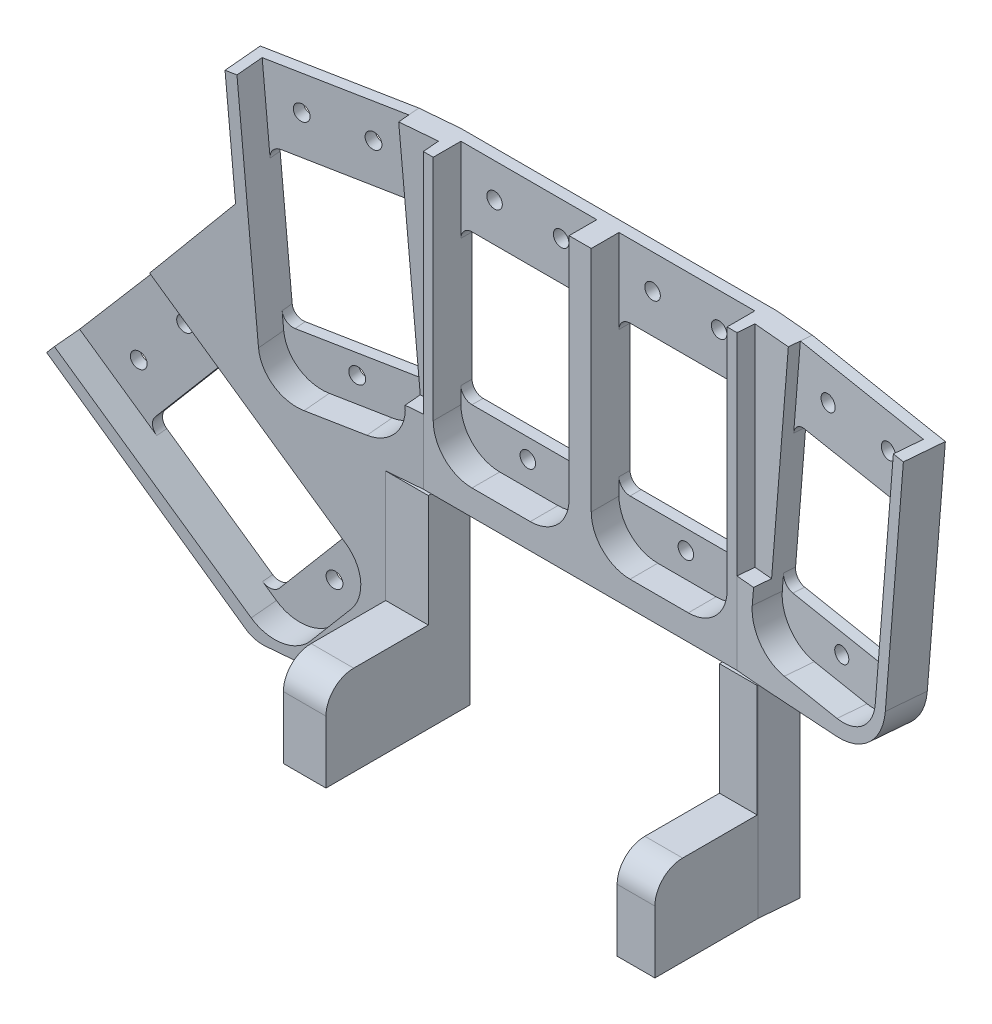
SolidWorks part; units mm, degrees
ref_plane "前视基准面" through (0, 0, 0) normal (0, 0, 1) x (1, 0, 0)
ref_plane "上视基准面" through (0, 0, 0) normal (0, 1, 0) x (1, 0, 0)
ref_plane "右视基准面" through (0, 0, 0) normal (1, 0, 0) x (0, 0, -1)
other "Configuration Table"
sketch "草图1" plane through (0, 0, 0) normal (0, 0, 1) x (1, 0, 0)
  line L0 (-6.3171, -14.436) -> (-6.3171, -11.436)
  line L1 (-8.3171, -13.436) -> (-28.8171, -13.436)
  line L2 (-30.8171, -11.436) -> (-30.8171, -14.436)
  line L3 (-23.8171, -21.436) -> (-13.3171, -21.436)
  line L4 (22.1829, -14.436) -> (22.1829, -11.436)
  line L5 (20.1829, -13.436) -> (-0.3171, -13.436)
  line L6 (-2.3171, -11.436) -> (-2.3171, -14.436)
  line L7 (4.6829, -21.436) -> (15.1829, -21.436)
  line L8 (22.1829, 11.564) -> (22.1829, 26.7199)
  line L9 (22.1829, 26.7199) -> (-2.3171, 26.7199)
  line L10 (-2.3171, 26.7199) -> (-2.3171, 11.564)
  line L11 (-0.3171, 13.564) -> (20.1829, 13.564)
  line L12 (-6.3171, 11.564) -> (-6.3171, 26.7199)
  line L13 (-6.3171, 26.7199) -> (-30.8171, 26.7199)
  line L14 (-30.8171, 26.7199) -> (-30.8171, 11.564)
  line L15 (-28.8171, 13.564) -> (-8.3171, 13.564)
  line L16 (-30.8171, 11.564) -> (-30.8171, -11.436)
  line L17 (-6.3171, 11.564) -> (-6.3171, -11.436)
  line L18 (22.1829, 11.564) -> (22.1829, -11.436)
  line L19 (-2.3171, 11.564) -> (-2.3171, -11.436)
  line L20 (-6.3171, 26.7199) -> (-2.3171, 26.7199)
  line L21 (-30.8171, 26.7199) -> (-32.8171, 26.7199)
  line L22 (-32.8171, 26.7199) -> (-32.8171, -25.4093)
  line L23 (-32.8171, -25.4093) -> (24.1829, -25.4093)
  line L24 (22.1829, 26.7199) -> (24.1829, 26.7199)
  line L25 (24.1829, 26.7199) -> (24.1829, -25.4093)
  arc A0 (-13.3171, -21.436) -> (-6.3171, -14.436) centre (-13.3171, -14.436) ccw
  arc A1 (-8.3171, -13.436) -> (-6.3171, -11.436) centre (-8.3171, -11.436) ccw
  arc A2 (-30.8171, -11.436) -> (-28.8171, -13.436) centre (-28.8171, -11.436) ccw
  arc A3 (-30.8171, -14.436) -> (-23.8171, -21.436) centre (-23.8171, -14.436) ccw
  arc A4 (15.1829, -21.436) -> (22.1829, -14.436) centre (15.1829, -14.436) ccw
  arc A5 (20.1829, -13.436) -> (22.1829, -11.436) centre (20.1829, -11.436) ccw
  arc A6 (-2.3171, -11.436) -> (-0.3171, -13.436) centre (-0.3171, -11.436) ccw
  arc A7 (-2.3171, -14.436) -> (4.6829, -21.436) centre (4.6829, -14.436) ccw
  arc A8 (-0.3171, 13.564) -> (-2.3171, 11.564) centre (-0.3171, 11.564) ccw
  arc A9 (22.1829, 11.564) -> (20.1829, 13.564) centre (20.1829, 11.564) ccw
  arc A10 (-28.8171, 13.564) -> (-30.8171, 11.564) centre (-28.8171, 11.564) ccw
  arc A11 (-6.3171, 11.564) -> (-8.3171, 13.564) centre (-8.3171, 11.564) ccw
sketch "草图2" plane through (0, 0, 0) normal (0, 0, 1) x (1, 0, 0)
  line L0 (-6.3171, -14.436) -> (-6.3171, -11.436)
  line L1 (-8.3171, -13.436) -> (-28.8171, -13.436)
  line L2 (-30.8171, -11.436) -> (-30.8171, -14.436)
  line L3 (-23.8171, -21.436) -> (-13.3171, -21.436)
  line L4 (22.1829, -14.436) -> (22.1829, -11.436)
  line L5 (20.1829, -13.436) -> (-0.3171, -13.436)
  line L6 (-2.3171, -11.436) -> (-2.3171, -14.436)
  line L7 (4.6829, -21.436) -> (15.1829, -21.436)
  line L8 (22.1829, 11.564) -> (22.1829, 26.7199)
  line L9 (22.1829, 26.7199) -> (-2.3171, 26.7199)
  line L10 (-2.3171, 26.7199) -> (-2.3171, 11.564)
  line L11 (-0.3171, 13.564) -> (20.1829, 13.564)
  line L12 (-6.3171, 11.564) -> (-6.3171, 26.7199)
  line L13 (-6.3171, 26.7199) -> (-30.8171, 26.7199)
  line L14 (-30.8171, 26.7199) -> (-30.8171, 11.564)
  line L15 (-28.8171, 13.564) -> (-8.3171, 13.564)
  line L16 (-30.8171, 11.564) -> (-30.8171, -11.436)
  line L17 (-6.3171, 11.564) -> (-6.3171, -11.436)
  line L18 (22.1829, 11.564) -> (22.1829, -11.436)
  line L19 (-2.3171, 11.564) -> (-2.3171, -11.436)
  line L20 (-6.3171, 26.7199) -> (-2.3171, 26.7199)
  line L21 (-30.8171, 26.7199) -> (-32.8171, 26.7199)
  line L22 (-32.8171, 26.7199) -> (-32.8171, -25.4093)
  line L23 (-32.8171, -25.4093) -> (24.1829, -25.4093)
  line L24 (22.1829, 26.7199) -> (24.1829, 26.7199)
  line L25 (24.1829, 26.7199) -> (24.1829, -25.4093)
  arc A0 (-13.3171, -21.436) -> (-6.3171, -14.436) centre (-13.3171, -14.436) ccw
  arc A1 (-8.3171, -13.436) -> (-6.3171, -11.436) centre (-8.3171, -11.436) ccw
  arc A2 (-30.8171, -11.436) -> (-28.8171, -13.436) centre (-28.8171, -11.436) ccw
  arc A3 (-30.8171, -14.436) -> (-23.8171, -21.436) centre (-23.8171, -14.436) ccw
  arc A4 (15.1829, -21.436) -> (22.1829, -14.436) centre (15.1829, -14.436) ccw
  arc A5 (20.1829, -13.436) -> (22.1829, -11.436) centre (20.1829, -11.436) ccw
  arc A6 (-2.3171, -11.436) -> (-0.3171, -13.436) centre (-0.3171, -11.436) ccw
  arc A7 (-2.3171, -14.436) -> (4.6829, -21.436) centre (4.6829, -14.436) ccw
  arc A8 (-0.3171, 13.564) -> (-2.3171, 11.564) centre (-0.3171, 11.564) ccw
  arc A9 (22.1829, 11.564) -> (20.1829, 13.564) centre (20.1829, 11.564) ccw
  arc A10 (-28.8171, 13.564) -> (-30.8171, 11.564) centre (-28.8171, 11.564) ccw
  arc A11 (-6.3171, 11.564) -> (-8.3171, 13.564) centre (-8.3171, 11.564) ccw
extrude "凸台-拉伸3" add sketch "草图1" along normal blind 2 contours A11 L12 L13 L14 A10 L15 | A9 L8 L9 L10 A8 L11 | L6 A7 L7 A4 L4 A5 L5 A6 | L2 A3 L3 A0 L0 A1 L1 A2 | A7 L6 L19 L10 L20 L12 L17 L0 A0 L3 A3 L2 L16 L14 L21 L22 L23 L25 L24 L8 L18 L4 A4 L7 region at (-18.5671, -17.1027, 0) region at (-4.3171, -7.8356, 0) region at (-18.5671, 20.1048, 0) region at (9.9329, 20.1048, 0) region at (9.9329, -17.1027, 0)
sketch "草图4" plane through (0, 0, 2) normal (0, 0, 1) x (1, 0, 0)
  line L0 (4.6829, -21.436) -> (15.1829, -21.436) construction
  line L1 (22.1829, -14.436) -> (22.1829, -11.436) construction
  line L2 (22.1829, 11.564) -> (22.1829, -11.436) construction
  line L3 (22.1829, 26.7199) -> (24.1829, 26.7199) construction
  line L4 (24.1829, 26.7199) -> (24.1829, -25.4093) construction
  line L5 (22.1829, 11.564) -> (22.1829, 26.7199) construction
  line L6 (-2.3171, 26.7199) -> (-2.3171, 11.564) construction
  line L7 (-2.3171, 11.564) -> (-2.3171, -11.436) construction
  line L8 (-2.3171, -11.436) -> (-2.3171, -14.436) construction
  line L9 (-32.8171, -25.4093) -> (24.1829, -25.4093) construction
  line L10 (-32.8171, 26.7199) -> (-32.8171, -25.4093) construction
  line L11 (-30.8171, 26.7199) -> (-32.8171, 26.7199) construction
  line L12 (-6.3171, 11.564) -> (-6.3171, 26.7199) construction
  line L13 (-6.3171, 11.564) -> (-6.3171, -11.436) construction
  line L14 (-6.3171, -14.436) -> (-6.3171, -11.436) construction
  line L15 (-23.8171, -21.436) -> (-13.3171, -21.436) construction
  line L16 (-30.8171, -11.436) -> (-30.8171, -14.436) construction
  line L17 (-30.8171, 11.564) -> (-30.8171, -11.436) construction
  line L18 (-30.8171, 26.7199) -> (-30.8171, 11.564) construction
  line L19 (4.6829, -21.436) -> (15.1829, -21.436)
  line L20 (22.1829, -14.436) -> (22.1829, -11.436)
  line L21 (22.1829, 11.564) -> (22.1829, -11.436)
  line L22 (22.1829, 26.7199) -> (24.1829, 26.7199)
  line L23 (24.1829, 26.7199) -> (24.1829, -25.4093)
  line L24 (22.1829, 11.564) -> (22.1829, 26.7199)
  line L25 (-2.3171, 26.7199) -> (-2.3171, 11.564)
  line L26 (-2.3171, 11.564) -> (-2.3171, -11.436)
  line L27 (-2.3171, -11.436) -> (-2.3171, -14.436)
  line L28 (-32.8171, -25.4093) -> (24.1829, -25.4093)
  line L29 (-32.8171, 26.7199) -> (-32.8171, -25.4093)
  line L30 (-30.8171, 26.7199) -> (-32.8171, 26.7199)
  line L31 (-6.3171, 11.564) -> (-6.3171, 26.7199)
  line L32 (-6.3171, 11.564) -> (-6.3171, -11.436)
  line L33 (-6.3171, -14.436) -> (-6.3171, -11.436)
  line L34 (-23.8171, -21.436) -> (-13.3171, -21.436)
  line L35 (-30.8171, -11.436) -> (-30.8171, -14.436)
  line L36 (-30.8171, 11.564) -> (-30.8171, -11.436)
  line L37 (-30.8171, 26.7199) -> (-30.8171, 11.564)
  line L38 (-6.3171, 26.7199) -> (-2.3171, 26.7199)
  arc A0 (15.1829, -21.436) -> (22.1829, -14.436) centre (15.1829, -14.436) ccw construction
  arc A1 (-2.3171, -14.436) -> (4.6829, -21.436) centre (4.6829, -14.436) ccw construction
  arc A2 (-13.3171, -21.436) -> (-6.3171, -14.436) centre (-13.3171, -14.436) ccw construction
  arc A3 (-30.8171, -14.436) -> (-23.8171, -21.436) centre (-23.8171, -14.436) ccw construction
  arc A4 (15.1829, -21.436) -> (22.1829, -14.436) centre (15.1829, -14.436) ccw
  arc A5 (-2.3171, -14.436) -> (4.6829, -21.436) centre (4.6829, -14.436) ccw
  arc A6 (-13.3171, -21.436) -> (-6.3171, -14.436) centre (-13.3171, -14.436) ccw
  arc A7 (-30.8171, -14.436) -> (-23.8171, -21.436) centre (-23.8171, -14.436) ccw
extrude "凸台-拉伸4" add sketch "草图4" along normal blind 5
sketch "草图5" plane through (0, 0, 2) normal (0, 0, 1) x (1, 0, 0)
  circle A0 centre (9.747, -16.936) radius 1.4
  circle A5 centre (-18.753, -16.936) radius 1.4
  circle A10 centre (-24.753, 20.564) radius 1.4
  circle A11 centre (-12.753, 20.564) radius 1.4
  circle A13 centre (3.747, 20.564) radius 1.4
  circle A14 centre (15.747, 20.564) radius 1.4
extrude "切除-拉伸1" cut sketch "草图5" against normal blind 5
sketch "草图7" plane through (0, 26.7199, 0) normal (0, 1, 0) x (1, 0, 0)
  line L0 (-32.8171, 0) -> (-70.2267, -3.2729)
  line L1 (-32.8171, -7) -> (-32.8171, 0) construction
  line L2 (-32.8171, 0) -> (-32.8171, -2)
  line L3 (-32.8171, -2) -> (-70.053, -5.2577)
  line L4 (-70.2267, -3.2729) -> (-70.053, -5.2577)
  dimension "D1" = 85
extrude "凸台-拉伸5" add sketch "草图7" against normal up to surface (52.1292 mm away) up to face at (-4.3171, -25.4093, 3.5)
sketch "草图8" plane through (-0.0756, 0, -0.8645) normal (0.0872, 0, 0.9962) x (0.9962, 0, -0.0872)
  line L0 (-36.1156, -14.2794) -> (-36.3771, -11.2908)
  line L2 (-60.7838, -13.4261) -> (-60.5224, -16.4147)
  line L4 (-38.3817, 11.6217) -> (-39.7026, 26.7199)
  line L5 (-39.7026, 26.7199) -> (-64.1093, 24.5846)
  line L6 (-64.1093, 24.5846) -> (-62.7884, 9.4864)
  line L8 (-62.7884, 9.4864) -> (-60.7838, -13.4261)
  line L9 (-38.3817, 11.6217) -> (-36.3771, -11.2908)
  line L10 (-70.2447, 26.7199) -> (-32.8666, 26.7199) construction
  line L11 (-36.1156, -14.2794) -> (-36.3771, -11.2908)
  line L12 (-38.1951, -13.4575) -> (-58.6171, -15.2442)
  line L13 (-52.9389, -22.7779) -> (-42.4789, -21.8628)
  line L14 (-60.9703, 11.6531) -> (-40.5484, 13.4398)
  line L15 (-38.3817, 11.6217) -> (-39.7026, 26.7199)
  arc A1 (-38.1951, -13.4575) -> (-36.3771, -11.2908) centre (-38.3695, -11.4651) ccw
  arc A2 (-60.7838, -13.4261) -> (-58.6171, -15.2442) centre (-58.7915, -13.2518) ccw
  arc A3 (-60.5224, -16.4147) -> (-52.9389, -22.7779) centre (-53.549, -15.8046) ccw
  arc A4 (-60.9703, 11.6531) -> (-62.7884, 9.4864) centre (-60.796, 9.6607) ccw
  arc A5 (-38.3817, 11.6217) -> (-40.5484, 13.4398) centre (-40.374, 11.4474) ccw
  circle A6 centre (-48.2863, -17.8537) radius 1.4
  arc A7 (-38.1951, -13.4575) -> (-36.3771, -11.2908) centre (-38.3695, -11.4651) ccw
  arc A8 (-42.4789, -21.8628) -> (-36.1156, -14.2794) centre (-43.089, -14.8894) ccw
  circle A9 centre (-57.5318, 18.9807) radius 1.4
  circle A10 centre (-45.5775, 20.0265) radius 1.4
  arc A11 (-38.3817, 11.6217) -> (-40.5484, 13.4398) centre (-40.374, 11.4474) ccw
extrude "切除-拉伸2" cut sketch "草图8" against normal blind 54 contours A9 | A10 | A6 | L9 A5 L14 A4 L8 A2 L12 A1 region at (-49.4697, -0.9022, 3.4569) region at (-48.1782, -17.8537, 3.3439) region at (-57.3885, 18.9807, 4.1497) region at (-45.4797, 20.0265, 3.1078)
sketch "草图9" plane through (-0.0756, 0, -0.8645) normal (0.0872, 0, 0.9962) x (0.9962, 0, -0.0872)
  line L0 (-38.3817, 11.6217) -> (-39.7026, 26.7199)
  line L1 (-70.2447, 26.7199) -> (-32.8666, 26.7199) construction
  line L2 (-39.7026, 26.7199) -> (-32.8666, 26.7199)
  line L3 (-32.8666, 26.7199) -> (-32.8666, -25.4093)
  line L4 (-32.8666, -25.4093) -> (-61.7354, -25.4093)
  line L5 (-60.7838, -13.4261) -> (-60.5224, -16.4147)
  line L6 (-60.7838, -13.4261) -> (-62.7884, 9.4864)
  line L7 (-62.7884, 9.4864) -> (-64.2962, 26.7199)
  line L8 (-64.2962, 26.7199) -> (-66.2962, 26.7199)
  line L9 (-66.2962, 26.7199) -> (-61.7354, -25.4093)
  line L10 (-60.7838, -13.4261) -> (-60.5224, -16.4147)
  line L11 (-36.1156, -14.2794) -> (-36.3771, -11.2908)
  line L13 (-52.9389, -22.7779) -> (-42.4789, -21.8628)
  line L14 (-38.3817, 11.6217) -> (-36.3771, -11.2908)
  circle A0 centre (-48.2863, -17.8537) radius 1.4
  arc A2 (-60.5224, -16.4147) -> (-52.9389, -22.7779) centre (-53.549, -15.8046) ccw
  arc A4 (-42.4789, -21.8628) -> (-36.1156, -14.2794) centre (-43.089, -14.8894) ccw
  line M17 (-70.2447, -25.4093) -> (-32.8666, -25.4093)
  line M18 (-32.8666, -25.4093) -> (-32.8666, 26.7199)
  line M19 (-32.8666, 26.7199) -> (-70.2447, 26.7199)
  line M22 (-38.3817, 11.6217) -> (-36.3771, -11.2908)
  line M26 (-60.7838, -13.4261) -> (-62.7884, 9.4864)
extrude "凸台-拉伸6" add sketch "草图9" along normal blind 5 contours A4 L13 A2 L5 L7 L9 L0 L11 M26 M19 M17 M18 M22 region at (-38.3546, 19.2248, 2.4845)
sketch "草图10" plane through (0, 26.7199, 0) normal (0, 1, 0) x (1, 0, 0)
  line L0 (24.1829, 0) -> (76.1307, -4.5448)
  line L1 (24.1829, -7) -> (24.1829, 0) construction
  line L3 (24.1829, -2) -> (76.1722, -6.5485)
  line L4 (76.1307, -4.5448) -> (76.1722, -6.5485)
  line L5 (24.1829, 0) -> (24.1829, -2)
  dimension "D1" = 85
extrude "凸台-拉伸7" add sketch "草图10" against normal up to surface (52.1292 mm away) up to face at (-35.0058, -25.4093, 4.568)
sketch "草图11" plane through (0.01, 0, -0.1148) normal (-0.0872, 0, 0.9962) x (0.9962, 0, 0.0872)
  line L0 (29.7802, 11.6217) -> (27.7757, -11.2908)
  line L1 (44.3375, -22.7779) -> (33.8775, -21.8628)
  line L2 (27.5142, -14.2794) -> (27.7757, -11.2908)
  line L3 (52.1824, -13.4261) -> (51.921, -16.4147)
  line L4 (57.6948, 26.7199) -> (53.134, -25.4093)
  line L5 (55.6948, 26.7199) -> (57.6948, 26.7199)
  line L6 (54.187, 9.4864) -> (55.6948, 26.7199)
  line L7 (52.1824, -13.4261) -> (54.187, 9.4864)
  line L8 (52.1824, -13.4261) -> (51.921, -16.4147)
  line L9 (24.2652, -25.4093) -> (53.134, -25.4093)
  line L10 (24.2652, 26.7199) -> (24.2652, -25.4093)
  line L11 (31.1012, 26.7199) -> (24.2652, 26.7199)
  line L12 (29.7802, 11.6217) -> (31.1012, 26.7199)
  arc A0 (33.8775, -21.8628) -> (27.5142, -14.2794) centre (34.4876, -14.8894) cw
  arc A1 (51.921, -16.4147) -> (44.3375, -22.7779) centre (44.9476, -15.8046) cw
  circle A2 centre (39.6849, -17.8537) radius 1.4
  line M1 (24.2652, -25.4093) -> (76.4531, -25.4093)
  line M3 (76.4531, 26.7199) -> (24.2652, 26.7199)
  line M4 (24.2652, 26.7199) -> (24.2652, -25.4093)
extrude "凸台-拉伸8" add sketch "草图11" along normal blind 5 contours L3 A1 L1 A0 L2 L0 L12 L4 L6 L7 M3 M4 M1 region at (28.0639, 0.2194, 2.3395)
sketch "草图12" plane through (0.01, 0, -0.1148) normal (-0.0872, 0, 0.9962) x (0.9962, 0, 0.0872)
  line L6 (50.0157, -15.2442) -> (29.5937, -13.4575)
  line L8 (31.9469, 13.4398) -> (52.3689, 11.6531)
  line L9 (29.7802, 11.6217) -> (27.7757, -11.2908)
  line L10 (54.187, 9.4864) -> (52.1824, -13.4261)
  circle A5 centre (36.6057, 20.0589) radius 1.4
  circle A6 centre (48.56, 19.0131) radius 1.4
  circle A7 centre (39.3145, -17.8213) radius 1.4
  arc A8 (27.7757, -11.2908) -> (29.5937, -13.4575) centre (29.768, -11.4651) ccw
  arc A10 (50.0157, -15.2442) -> (52.1824, -13.4261) centre (50.19, -13.2518) ccw
  arc A12 (54.187, 9.4864) -> (52.3689, 11.6531) centre (52.1946, 9.6607) ccw
  arc A13 (31.9469, 13.4398) -> (29.7802, 11.6217) centre (31.7726, 11.4474) ccw
extrude "切除-拉伸3" cut sketch "草图12" against normal blind 5
sketch "草图14" plane through (0, -25.4093, 0) normal (0, -1, 0) x (1, 0, 0)
  line L12 (52.5061, 9.4971) -> (23.9646, 7)
  line L13 (23.9646, 7) -> (-32.5988, 7)
  line L14 (-32.5988, 7) -> (-61.1404, 9.4971)
  line L15 (-61.1404, 9.4971) -> (-61.5762, 4.5161)
  line L16 (-61.5762, 4.5161) -> (-70.053, 5.2577)
  line L17 (-70.053, 5.2577) -> (-70.2267, 3.2729)
  line L18 (-70.2267, 3.2729) -> (-32.8171, 0)
  line L19 (-32.8171, 0) -> (24.1829, 0)
  line L20 (24.1829, 0) -> (76.1307, 4.5448)
  line L21 (76.1307, 4.5448) -> (76.1722, 6.5485)
  line L22 (76.1722, 6.5485) -> (52.9419, 4.5161)
  line L23 (52.9419, 4.5161) -> (52.5061, 9.4971)
  line L24 (52.5061, 9.4971) -> (23.9646, 7)
  line L26 (-32.5988, 7) -> (-61.1404, 9.4971)
  line L27 (-61.1404, 9.4971) -> (-61.5762, 4.5161)
  line L28 (-61.5762, 4.5161) -> (-70.053, 5.2577)
  line L29 (-70.053, 5.2577) -> (-70.2267, 3.2729)
  line L30 (-70.2267, 3.2729) -> (-32.8171, 0)
  line L31 (-32.8171, 0) -> (24.1829, 0)
  line L32 (24.1829, 0) -> (76.1307, 4.5448)
  line L33 (76.1307, 4.5448) -> (76.1722, 6.5485)
  line L34 (76.1722, 6.5485) -> (52.9419, 4.5161)
  line L35 (52.9419, 4.5161) -> (52.5061, 9.4971)
  line L36 (23.9646, 7) -> (-32.5988, 7)
  dimension "D1" = 0
extrude "凸台-拉伸9" add sketch "草图14" along normal blind 48
sketch "草图16" plane through (-69.9774, 0, 6.1222) normal (-0.9962, 0, 0.0872) x (0.0872, 0, 0.9962)
  line L4 (-2.8602, 26.7199) -> (-2.8602, -73.4093)
  line L5 (-2.8602, -73.4093) -> (-0.8678, -73.4093)
  line L6 (-0.8678, -73.4093) -> (-0.8678, 26.7199)
  line L7 (-0.8678, 26.7199) -> (-2.8602, 26.7199)
  line L8 (-2.8602, 26.7199) -> (-2.8602, -73.4093)
  line L9 (-2.8602, -73.4093) -> (-0.8678, -73.4093)
  line L10 (-0.8678, -73.4093) -> (-0.8678, 26.7199)
  line L11 (-0.8678, 26.7199) -> (-2.8602, 26.7199)
  dimension "D1" = 0
extrude "凸台-拉伸10" add sketch "草图16" along normal blind 31
sketch "草图19" plane through (-0.0756, 0, -0.8645) normal (0.0872, 0, 0.9962) x (0.9962, 0, -0.0872)
  line L5 (-66.2962, 26.7199) -> (-101.2447, 26.7199)
  line L6 (-101.2447, 26.7199) -> (-101.2447, -73.4093)
  line L7 (-101.2447, -73.4093) -> (-61.7354, -73.4093)
  line L8 (-61.7354, -73.4093) -> (-61.7354, -25.4093)
  line L9 (-61.7354, -25.4093) -> (-66.2962, 26.7199)
  line L10 (-66.2962, 26.7199) -> (-101.2447, 26.7199)
  line L11 (-101.2447, 26.7199) -> (-101.2447, -73.4093)
  line L12 (-101.2447, -73.4093) -> (-61.7354, -73.4093)
  line L13 (-61.7354, -73.4093) -> (-61.7354, -25.4093)
  line L14 (-61.7354, -25.4093) -> (-66.2962, 26.7199)
  dimension "D1" = 0
extrude "凸台-拉伸12" add sketch "草图19" along normal blind 5 contours L10 L11 L12 L13 L14
sketch "草图20" plane through (0.3601, 0, 4.1165) normal (0.0872, 0, 0.9962) x (0.9962, 0, -0.0872)
  line L0 (-45.9906, -40.369) -> (-48.2888, -38.4406)
  line L1 (-48.0423, -41.2583) -> (-61.2194, -56.9622)
  line L2 (-64.0371, -57.2087) -> (-61.7389, -59.1371)
  line L3 (-51.8771, -58.2743) -> (-45.1278, -50.2308)
  line L4 (-78.6472, -12.9668) -> (-94.4978, -31.6491)
  line L5 (-94.4978, -31.6491) -> (-81.6561, -42.4246)
  line L6 (-81.9026, -39.6069) -> (-68.7255, -23.903)
  line L7 (-65.9078, -23.6565) -> (-78.6472, -12.9668)
  line L8 (-81.6561, -42.4246) -> (-64.0371, -57.2087)
  line L9 (-65.9078, -23.6565) -> (-48.2888, -38.4406)
  arc A0 (-45.1278, -50.2308) -> (-45.9906, -40.369) centre (-50.4902, -45.7313) ccw
  arc A1 (-48.0423, -41.2583) -> (-48.2888, -38.4406) centre (-49.5744, -39.9727) ccw
  arc A2 (-64.0371, -57.2087) -> (-61.2194, -56.9622) centre (-62.7515, -55.6766) ccw
  arc A3 (-61.7389, -59.1371) -> (-51.8771, -58.2743) centre (-57.2394, -53.7747) ccw
  arc A4 (-81.9026, -39.6069) -> (-81.6561, -42.4246) centre (-80.3705, -40.8925) ccw
  arc A5 (-65.9078, -23.6565) -> (-68.7255, -23.903) centre (-67.1934, -25.1886) ccw
  circle A6 centre (-76.9391, -22.8016) radius 1.4
  circle A7 centre (-84.6526, -31.9941) radius 1.4
  circle A8 centre (-52.0692, -51.5024) radius 1.4
extrude "切除-拉伸4" cut sketch "草图20" against normal blind 5 contours L9 A5 L6 A4 L8 A2 L1 A1 | A6 | A7 | A5 L7 L4 L5 A4 L6 A7 A6 | L2 A3 L3 A0 L0 A1 L1 A2 A8 | A8 region at (-43.2922, -45.1476, 7.9356) region at (-64.3651, -40.4326, 9.7792) region at (-80.2633, -27.0578, 11.1701) region at (-76.2862, -22.8016, 10.8222) region at (-83.9703, -31.9941, 11.4944) region at (-51.5109, -51.5024, 8.6546)
sketch "草图22" plane through (-0.0756, 0, -0.8645) normal (0.0872, 0, 0.9962) x (0.9962, 0, -0.0872)
  circle A6 centre (-76.9391, -22.8016) radius 1.4
  circle A7 centre (-84.6526, -31.9941) radius 1.4
  circle A8 centre (-52.0692, -51.5024) radius 1.4
extrude "切除-拉伸5" cut sketch "草图22" against normal through all
sketch "草图23" plane through (-0.0756, 0, -0.8645) normal (0.0872, 0, 0.9962) x (0.9962, 0, -0.0872)
  line L1 (-48.0423, -41.2583) -> (-61.2194, -56.9622)
  line L6 (-81.9026, -39.6069) -> (-68.7255, -23.903)
  line L8 (-81.6561, -42.4246) -> (-64.0371, -57.2087)
  line L9 (-65.9078, -23.6565) -> (-48.2888, -38.4406)
  arc A1 (-48.0423, -41.2583) -> (-48.2888, -38.4406) centre (-49.5744, -39.9727) ccw
  arc A2 (-64.0371, -57.2087) -> (-61.2194, -56.9622) centre (-62.7515, -55.6766) ccw
  arc A4 (-81.9026, -39.6069) -> (-81.6561, -42.4246) centre (-80.3705, -40.8925) ccw
  arc A5 (-65.9078, -23.6565) -> (-68.7255, -23.903) centre (-67.1934, -25.1886) ccw
extrude "切除-拉伸6" cut sketch "草图23" against normal through all
sketch "草图24" plane through (0.3601, 0, 4.1165) normal (0.0872, 0, 0.9962) x (0.9962, 0, -0.0872)
  line L0 (-78.6472, -12.9668) -> (-94.4978, -31.6491)
  line L1 (-48.3684, -73.4093) -> (-101.2447, -73.4093)
  line L6 (-64.2962, 26.7199) -> (-101.2447, 26.7199) construction
  line L7 (-66.2962, 26.7199) -> (-64.3389, 4.3484)
  line L8 (-78.6472, -12.9668) -> (-64.3389, 4.3484)
  line L9 (-66.2962, 26.7199) -> (-101.2447, 26.7199)
  line L10 (-101.2447, 26.7199) -> (-101.2447, -73.4093)
  line L11 (-94.4978, -31.6491) -> (-95.7917, -33.1742)
  line L12 (-95.7917, -33.1742) -> (-48.3684, -73.4093)
  line L13 (-33.0849, -73.4093) -> (-101.2447, -73.4093) construction
extrude "切除-拉伸7" cut sketch "草图24" against normal through all
sketch "草图25" plane through (0, 0, 7) normal (0, 0, 1) x (1, 0, 0)
  line L8 (28.1628, -26.0179) -> (21.3541, -26.0179)
  line L9 (21.3541, -26.0179) -> (21.3541, -62.4789)
  line L10 (21.3541, -62.4789) -> (28.1628, -62.4789)
  line L11 (28.1628, -62.4789) -> (28.1628, -26.0179)
  line L12 (-38.8372, -62.4789) -> (-31.1575, -62.4789)
  line L13 (-31.1575, -62.4789) -> (-31.1575, -26.0179)
  line L14 (-31.1575, -26.0179) -> (-38.8372, -26.0179)
  line L15 (-38.8372, -26.0179) -> (-38.8372, -62.4789)
extrude "凸台-拉伸14" add sketch "草图25" along normal blind 19
sketch "草图26" plane through (0, 0, 7) normal (0, 0, 1) x (1, 0, 0)
  line L1 (-38.8372, -62.4789) -> (76.1722, -62.4789)
  line L2 (-38.8372, -62.4789) -> (-38.8372, -73.4093)
  line L3 (-38.8372, -73.4093) -> (76.1722, -73.4093)
  line L4 (76.1722, -62.4789) -> (76.1722, -73.4093)
  line L5 (-38.8372, -62.4789) -> (-63.6236, -62.4789)
  line L6 (-38.8372, -62.4789) -> (-38.8372, -73.4093)
  line L7 (-38.8372, -73.4093) -> (-63.6236, -73.4093)
  line L8 (-63.6236, -62.4789) -> (-63.6236, -73.4093)
  line M24 (-31.1575, -62.4789) -> (-32.5988, -62.4789)
  line M25 (-32.5988, -62.4789) -> (-32.5988, -73.4093)
  line M26 (-32.5988, -73.4093) -> (23.9646, -73.4093)
  line M27 (23.9646, -73.4093) -> (23.9646, -62.4789)
  line M28 (23.9646, -62.4789) -> (21.3541, -62.4789)
extrude "切除-拉伸8" cut sketch "草图26" against normal through all and the other way through all contours L5 L8 L7 L2 | L1 M24 M25 M26 M27 M28 | L4 L1 L3 M27 | L2 L3 L1 M25 region at (-35.718, -67.9441, 7) region at (-51.2304, -67.9441, 7) region at (-4.3171, -67.9441, 7) region at (50.0684, -67.9441, 7)
sketch "草图27" plane through (-0.4257, 0, 4.8661) normal (-0.0872, 0, 0.9962) x (0.9962, 0, 0.0872)
  line L1 (57.6948, 26.7199) -> (53.134, -25.4093) construction
  line L2 (57.6948, 26.7199) -> (53.134, -25.4093) construction
  line L3 (53.134, -25.4093) -> (28.6978, -26.0179)
  line L4 (28.6978, -26.0179) -> (28.6978, -62.4789)
  line L5 (28.6978, -62.4789) -> (53.134, -62.4789)
  line L7 (53.134, -62.4789) -> (53.134, -25.4093)
extrude "切除-拉伸9" cut sketch "草图27" against normal through all contours L3 L4 L5 L7
sketch "草图28" plane through (0.01, 0, -0.1148) normal (-0.0872, 0, 0.9962) x (0.9962, 0, 0.0872)
  line L5 (53.134, -62.4789) -> (76.4531, -62.4789)
  line L6 (76.4531, -62.4789) -> (76.4531, 26.7199)
  line L7 (76.4531, 26.7199) -> (57.6948, 26.7199)
  line L8 (57.6948, 26.7199) -> (53.134, -25.4093)
  line L11 (76.4531, -62.4789) -> (76.4531, 26.7199)
  line L12 (76.4531, 26.7199) -> (57.6948, 26.7199)
  line L13 (57.6948, 26.7199) -> (53.134, -25.4093)
  line L15 (53.134, -62.4789) -> (76.4531, -62.4789)
  line L17 (53.134, -25.4093) -> (53.134, -62.4789)
  line L18 (53.134, -25.4093) -> (53.134, -62.4789)
  dimension "D1" = 0
extrude "切除-拉伸10" cut sketch "草图28" against normal through all
sketch "草图29" plane through (-0.0756, 0, -0.8645) normal (0.0872, 0, 0.9962) x (0.9962, 0, -0.0872)
  line L0 (-39.7026, 26.7199) -> (-66.0942, 24.411)
  line L1 (-64.3389, 4.3484) -> (-66.2962, 26.7199) construction
  line L2 (-66.0942, 24.411) -> (-66.2962, 26.7199)
  line L3 (-66.2962, 26.7199) -> (-39.7026, 26.7199)
extrude "切除-拉伸11" cut sketch "草图29" against normal through all and the other way through all
sketch "草图31" plane through (0.01, 0, -0.1148) normal (-0.0872, 0, 0.9962) x (0.9962, 0, 0.0872)
  line L0 (31.1012, 26.7199) -> (57.4927, 24.411)
  line L1 (57.6948, 26.7199) -> (53.134, -25.4093) construction
  line L2 (57.4927, 24.411) -> (57.6948, 26.7199)
  line L3 (57.6948, 26.7199) -> (31.1012, 26.7199)
extrude "切除-拉伸13" cut sketch "草图31" against normal through all and the other way through all
sketch "草图32" plane through (0.3601, 0, 4.1165) normal (0.0872, 0, 0.9962) x (0.9962, 0, -0.0872)
  line L14 (-61.2515, -62.4789) -> (-39.347, -62.4789)
  line L15 (-39.347, -62.4789) -> (-39.347, -26.0179)
  line L16 (-64.1093, 24.5846) -> (-66.0942, 24.411)
  line L17 (-66.0942, 24.411) -> (-64.3389, 4.3484)
  line L18 (-64.3389, 4.3484) -> (-78.6472, -12.9668)
  line L19 (-78.6472, -12.9668) -> (-45.9906, -40.369)
  line L20 (-45.1278, -50.2308) -> (-51.8771, -58.2743)
  line L21 (-61.7389, -59.1371) -> (-94.4978, -31.6491)
  line L22 (-94.4978, -31.6491) -> (-95.7917, -33.1742)
  line L23 (-95.7917, -33.1742) -> (-61.2515, -62.4789)
  line L26 (-39.347, -62.4789) -> (-39.347, -26.0179)
  line L28 (-33.0849, 26.7199) -> (-39.7026, 26.7199)
  line L29 (-39.7026, 26.7199) -> (-36.1156, -14.2794)
  line L30 (-42.4789, -21.8628) -> (-52.9389, -22.7779)
  line L31 (-60.5224, -16.4147) -> (-64.1093, 24.5846)
  line L45 (-39.347, -26.0179) -> (-33.0849, -26.0179)
  line L46 (-33.0849, -26.0179) -> (-33.0849, 26.7199)
  arc A4 (-45.1278, -50.2308) -> (-45.9906, -40.369) centre (-50.4902, -45.7313) ccw
  arc A5 (-61.7389, -59.1371) -> (-51.8771, -58.2743) centre (-57.2394, -53.7747) ccw
  arc A6 (-42.4789, -21.8628) -> (-36.1156, -14.2794) centre (-43.089, -14.8894) ccw
  arc A7 (-60.5224, -16.4147) -> (-52.9389, -22.7779) centre (-53.549, -15.8046) ccw
  dimension "D1" = 0
sketch "草图33" plane through (0.3601, 0, 4.1165) normal (0.0872, 0, 0.9962) x (0.9962, 0, -0.0872)
  line L0 (-39.7026, 26.7199) -> (-33.0849, 26.7199)
  line L1 (-36.1156, -14.2794) -> (-33.0849, -14.2794)
  line L2 (-33.0849, 26.7199) -> (-33.0849, -14.2794)
  line L3 (-33.0849, -26.0179) -> (-33.0849, 26.7199) construction
  line L4 (-36.1156, -14.2794) -> (-39.7026, 26.7199)
extrude "切除-拉伸15" cut sketch "草图33" against normal blind 3
sketch "草图34" plane through (-0.4257, 0, 4.8661) normal (-0.0872, 0, 0.9962) x (0.9962, 0, 0.0872)
  line L0 (31.1012, 26.7199) -> (27.7757, -11.2908)
  line L1 (27.7757, -11.2908) -> (24.4835, -11.2908)
  line L2 (24.4835, 26.7199) -> (24.4835, -26.0179) construction
  line L3 (24.4835, -11.2908) -> (24.4835, 26.7199)
  line L4 (24.4835, 26.7199) -> (31.1012, 26.7199)
extrude "切除-拉伸16" cut sketch "草图34" against normal blind 3
sketch "草图35" plane through (0, 0, 7) normal (0, 0, 1) x (1, 0, 0)
  line L1 (-31.1575, -26.0179) -> (21.3541, -26.0179)
  line L2 (-31.1575, -26.0179) -> (-31.1575, -62.4789)
  line L3 (-31.1575, -62.4789) -> (21.3541, -62.4789)
  line L4 (21.3541, -26.0179) -> (21.3541, -62.4789)
extrude "切除-拉伸18" cut sketch "草图35" against normal blind 11
sketch "草图36" plane through (0, -62.4789, 0) normal (0, -1, 0) x (1, 0, 0)
  circle A0 centre (25.0484, 3) radius 1.4
  circle A1 centre (25.0484, 21) radius 1.4
  circle A2 centre (-35.9516, 3) radius 1.4
  circle A3 centre (-35.9516, 21) radius 1.4
extrude "切除-拉伸19" cut sketch "草图36" against normal blind 5
fillet "圆角1" radius 10 1 edges at (52.8108, -25.4093, 6.0142)
sketch "草图37" plane through (-38.8372, 0, 0) normal (-1, 0, 0) x (0, 0, 1)
  line L0 (7.5458, -62.4789) -> (7.5458, -26.0179) construction
  line L1 (26, -26.0179) -> (7.5458, -26.0179)
  line L2 (26, -26.0179) -> (26, -46.246)
  line L3 (26, -46.246) -> (7.5458, -46.246)
  line L4 (7.5458, -26.0179) -> (7.5458, -46.246)
extrude "切除-拉伸20" cut sketch "草图37" against normal blind 67
fillet "圆角2" radius 5 3 edges at (-60.963, -62.4789, 5.972) (24.7585, -46.246, 26) (-34.9973, -46.246, 26)
